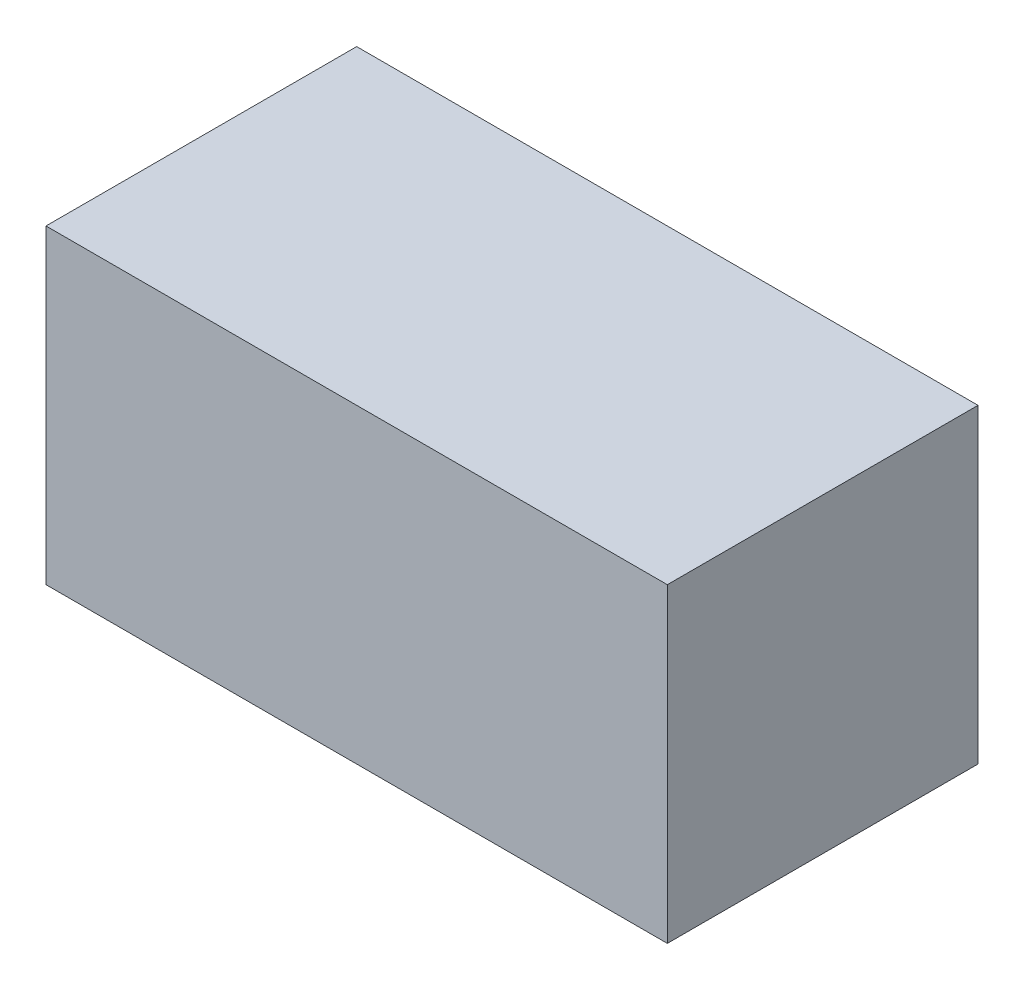
SolidWorks part; units mm, degrees
material "Alloy Steel"
ref_plane "Front Plane" through (0, 0, 0) normal (0, 0, 1) x (1, 0, 0)
ref_plane "Top Plane" through (0, 0, 0) normal (0, 1, 0) x (1, 0, 0)
ref_plane "Right Plane" through (0, 0, 0) normal (1, 0, 0) x (0, 0, -1)
sketch "Sketch1" plane through (0, 0, 0) normal (1, 0, 0) x (0, 0, -1)
  line L1 (-2, -2) -> (2, -2)
  line L2 (-2, -2) -> (-2, 2)
  line L3 (-2, 2) -> (2, 2)
  line L4 (2, -2) -> (2, 2)
  line L5 (-2, -2) -> (2, 2) construction
  line L6 (-2, 2) -> (2, -2) construction
  point P0 (0, 0)
  dimension "D1" = 4
  dimension "D2" = 4
extrude "Boss-Extrude1" add sketch "Sketch1" along normal mid plane 12
sketch "Sketch2" plane through (0, 2, 0) normal (0, 1, 0) x (1, 0, 0)
  line L0 (6, -2) -> (-6, -2) construction
  line L1 (6, 2) -> (2, 2)
  line L2 (6, 2) -> (6, -2)
  line L3 (6, -2) -> (2, -2)
  line L4 (2, 2) -> (2, -2)
  dimension "D1" = 4
extrude "Cut-Extrude1" cut sketch "Sketch2" against normal through all
equation "\"shaft-diameter\" =20mm"
equation "\"key-length\"=12mm"
equation "\"key-width\"=4mm"
equation "\"D1@Boss-Extrude1\"=\"key-length\""
equation "\"D2@Sketch1\"=\"key-width\""
